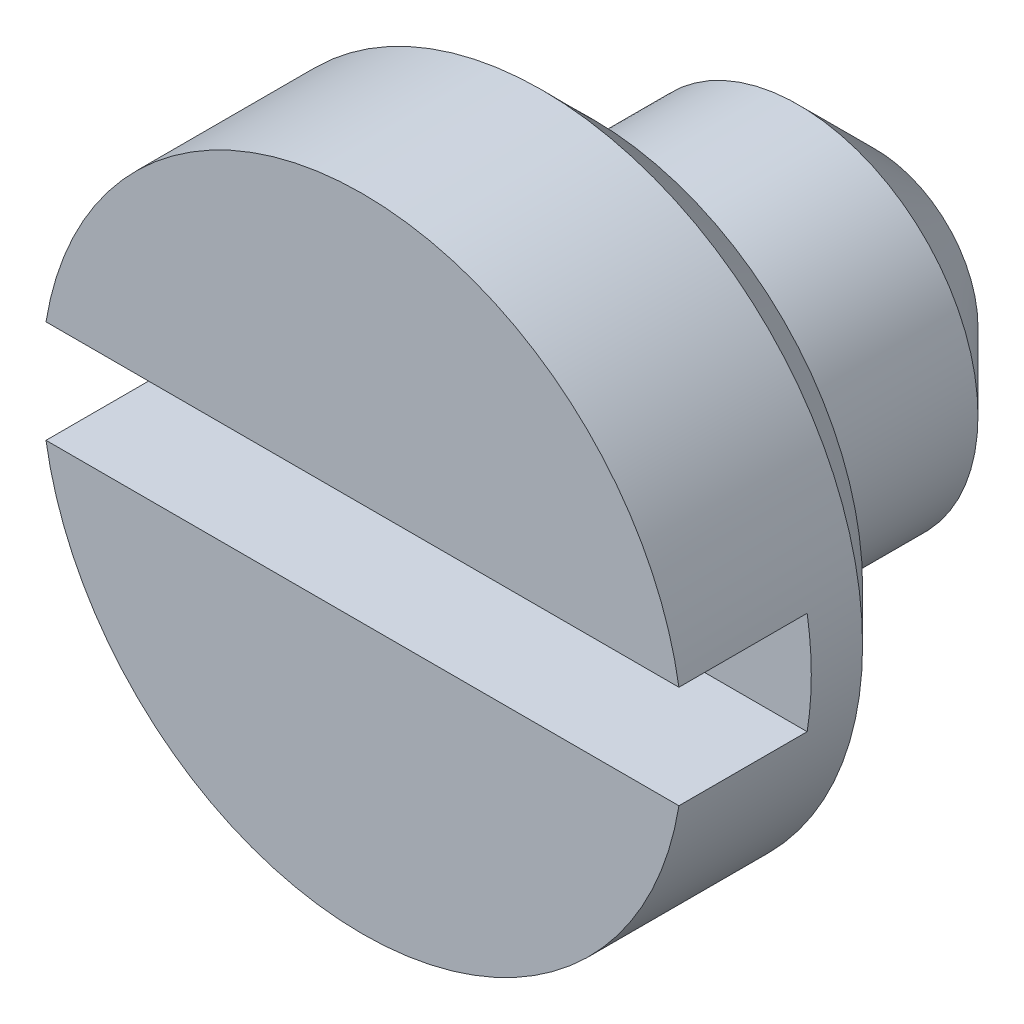
SolidWorks part; units mm, degrees
ref_plane "Front Plane" through (0, 0, 0) normal (0, 0, 1) x (1, 0, 0)
ref_plane "Top Plane" through (0, 0, 0) normal (0, 1, 0) x (1, 0, 0)
ref_plane "Right Plane" through (0, 0, 0) normal (1, 0, 0) x (0, 0, -1)
sketch "Sketch1" plane through (0, 0, 0) normal (0, 0, 1) x (1, 0, 0)
  circle A0 centre (0, 0) radius 1.25
  dimension "D1" = 2.5
extrude "Boss-Extrude1" add sketch "Sketch1" against normal blind 2 contours A0
sketch "Sketch2" plane through (0, 0, -2) normal (0, 0, -1) x (-1, 0, 0)
  circle A0 centre (0, 0) radius 0.7
  dimension "D1" = 1.4
extrude "Cut-Extrude1" cut sketch "Sketch2" against normal blind 1.1 flip side to cut
cosmetic thread "Cosmetic Thread1" parameters "D2"=1.15
sketch "Sketch3" plane through (0, 0, 0) normal (0, 0, 1) x (1, 0, 0)
  line L1 (-1.35, -0.2) -> (1.35, -0.2)
  line L2 (-1.35, -0.2) -> (-1.35, 0.2)
  line L3 (-1.35, 0.2) -> (1.35, 0.2)
  line L4 (1.35, -0.2) -> (1.35, 0.2)
  line L5 (-1.35, -0.2) -> (1.35, 0.2) construction
  line L6 (-1.35, 0.2) -> (1.35, -0.2) construction
  circle A0 centre (0, 0) radius 1.25 construction
  point P0 (0, 0)
  dimension "D2" = 0.1
  dimension "D1" = 0.4
extrude "Cut-Extrude2" cut sketch "Sketch3" against normal blind 0.5
chamfer "Chamfer1" distance 0.2 angle 45 1 edges at (-1.25, 0, -0.9)
chamfer "Chamfer2" distance 0.3 angle 45 1 edges at (-0.7, 0, -2)
